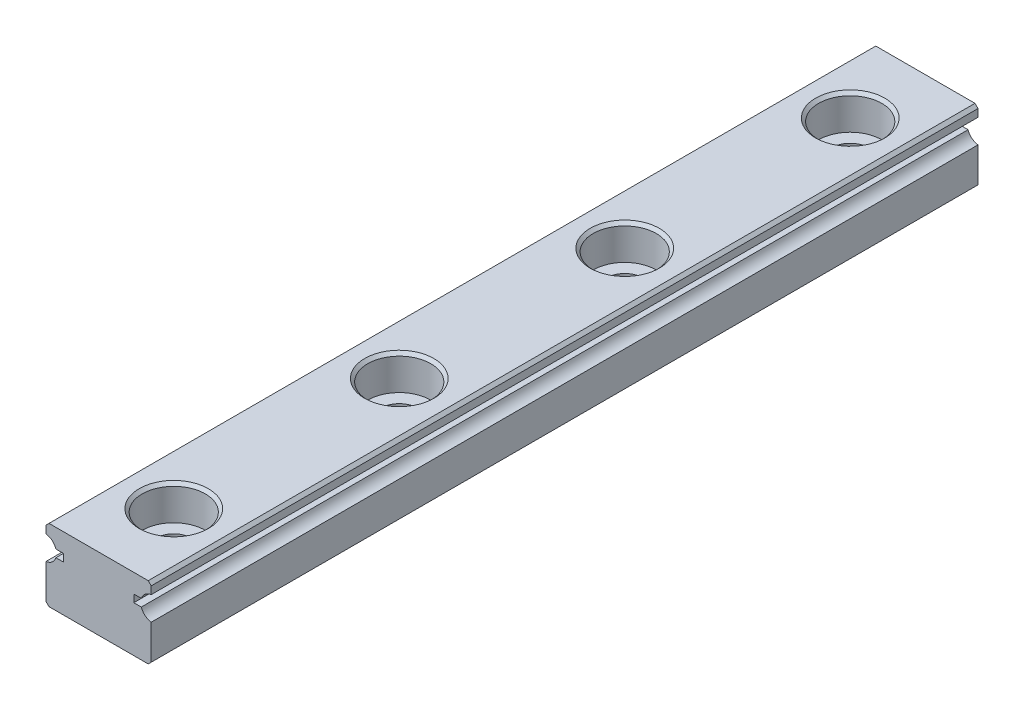
SolidWorks part; units mm, degrees
ref_plane "Спереди" through (0, 0, 0) normal (0, 0, 1) x (1, 0, 0)
ref_plane "Сверху" through (0, 0, 0) normal (0, 1, 0) x (1, 0, 0)
ref_plane "Справа" through (0, 0, 0) normal (1, 0, 0) x (0, 0, -1)
sketch "Sketch1" plane through (0, 0, 0) normal (0, 0, 1) x (1, 0, 0)
  line L0 (0, 0) -> (0, 4.3706) construction
  line L1 (-3.3, -2.4) -> (3.3, -2.4)
  line L2 (-3.5, -2.2) -> (-3.5, 0.1063)
  line L3 (-3.3, 2.4) -> (3.3, 2.4)
  line L4 (3.5, -2.2) -> (3.5, 0.1063)
  line L5 (-3.5, -2.4) -> (3.5, 2.4) construction
  line L6 (-3.5, 2.4) -> (3.5, -2.4) construction
  line L7 (-3.5, 1.6937) -> (-3.5, 2.2)
  line L8 (3.5, 1.6937) -> (3.5, 2.2)
  line L9 (-3.5, -2.2) -> (-3.3, -2.4)
  line L10 (3.3, -2.4) -> (3.5, -2.2)
  line L11 (3.3, 2.4) -> (3.5, 2.2)
  line L12 (-3.5, 2.2) -> (-3.3, 2.4)
  line L13 (2.8401, 0.65) -> (2.3401, 0.65)
  line L14 (-2.8401, 0.65) -> (-2.3401, 0.65)
  line L15 (2.3401, 0.65) -> (2.3401, 1.15)
  line L16 (-2.8401, 1.15) -> (-2.3401, 1.15)
  line L17 (-2.3401, 0.65) -> (-2.3401, 1.15)
  line L18 (2.8401, 1.15) -> (2.3401, 1.15)
  arc A0 (-3.5, 1.6937) -> (-2.8401, 1.15) centre (-3.6, 0.9) cw
  arc A1 (3.5, 1.6937) -> (2.8401, 1.15) centre (3.6, 0.9) ccw
  arc A2 (-2.8401, 0.65) -> (-3.5, 0.1063) centre (-3.6, 0.9) cw
  arc A3 (2.8401, 0.65) -> (3.5, 0.1063) centre (3.6, 0.9) ccw
  point P0 (0, 0)
  dimension "D4" = 0.8
  dimension "D5" = 0.1
  dimension "D1" = 7
  dimension "D2" = 4.8
  dimension "D3" = 1.5
  dimension "D6" = 0.5
  dimension "D7" = 0.5
extrude "Extrude1" add sketch "Sketch1" along normal blind 55
sketch "Sketch2" plane through (0, 2.4, 0) normal (0, 1, 0) x (1, 0, 0)
  line L0 (0, 0) -> (0, -5) construction
  circle A0 centre (0, -5) radius 1.2
  circle A1 centre (0, -5) radius 2.1
  dimension "D1" = 2.4
  dimension "D2" = 4.2
  dimension "D3" = 5
extrude "Extrude2" cut sketch "Sketch2" against normal up to next contours A0 region at (0, 2.4, 5)
extrude "Extrude4" cut sketch "Sketch" against normal blind 2.3
sketch "Sketch" plane through (0, 2.4, 0) normal (0, 1, 0) x (1, 0, 0) same geometry as "Sketch2"
chamfer "Chamfer1" distance 0.2 angle 45 2 edges at (0, -2.4, 6.2) (0, 2.4, 7.1)
pattern_linear "LPattern1" count 4 spacing 15 along (0, 0, 1) of "Extrude4", "Chamfer1", "Extrude2"
